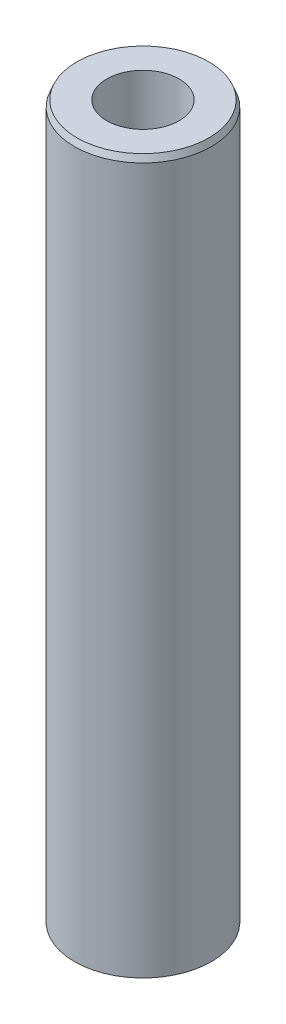
SolidWorks part; units mm, degrees
ref_plane "Front Plane" through (0, 0, 0) normal (0, 0, 1) x (1, 0, 0)
ref_plane "Top Plane" through (0, 0, 0) normal (0, 1, 0) x (1, 0, 0)
ref_plane "Right Plane" through (0, 0, 0) normal (1, 0, 0) x (0, 0, -1)
sketch "Sketch1" plane through (0, 0, 0) normal (0, 1, 0) x (1, 0, 0)
  circle A0 centre (0, 0) radius 57.5
  dimension "SHAFT_OD" = 115
extrude "Boss-Extrude1" add sketch "Sketch1" along normal blind 600
sketch "Sketch2" plane through (0, 0, 0) normal (0, 1, 0) x (1, 0, 0)
  circle A0 centre (0, 0) radius 30.4094
  dimension "BORE_D" = 60.8187
extrude "Cut-Extrude1" cut sketch "Sketch2" along normal through all
chamfer "Chamfer1" distance 5.289 angle 22.134 2 edges at (0, 600, 57.5) (0, 0, 57.5) first distance on face at (0, 600, 57.5) first distance on face at (0, 0, 30.4094)
